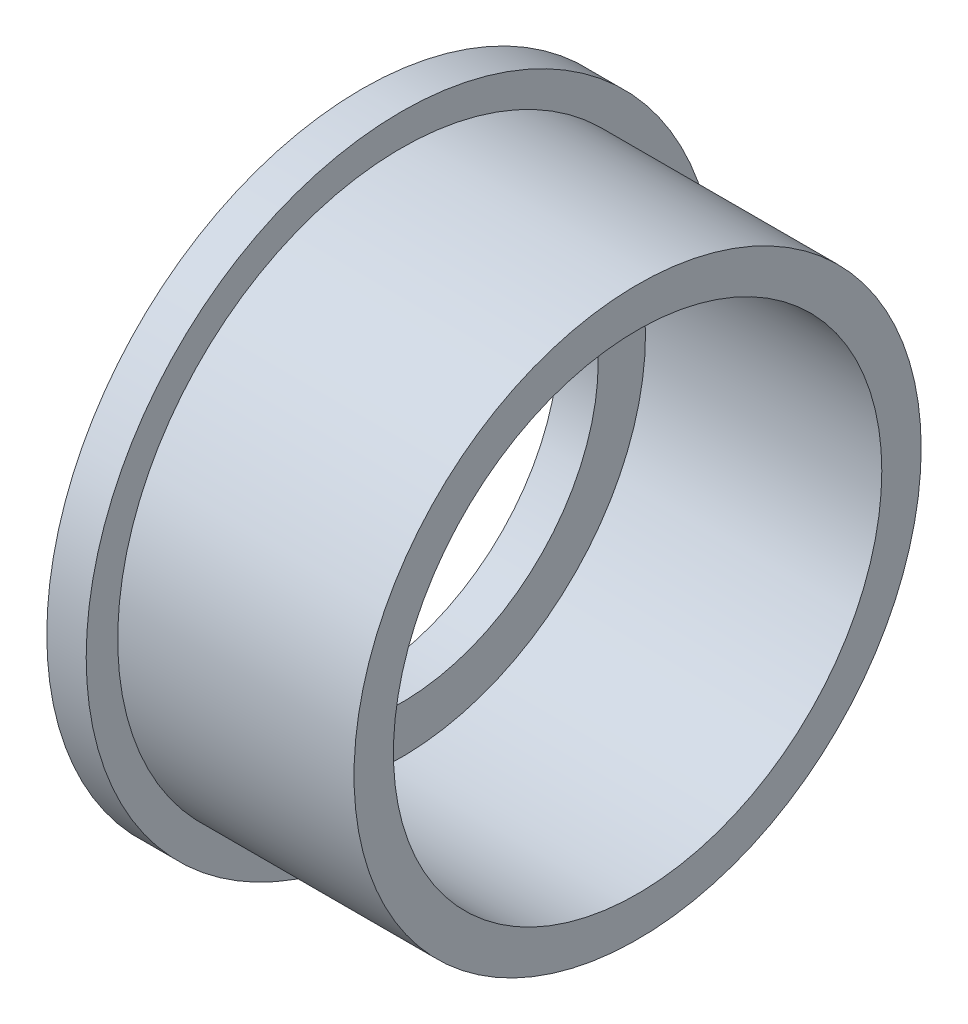
SolidWorks part; units mm, degrees
ref_plane "Front Plane" through (0, 0, 0) normal (1, 0, 0) x (0, 1, 0)
ref_plane "Top Plane" through (0, 0, 0) normal (0, 0, 1) x (0, 1, 0)
ref_plane "Right Plane" through (0, 0, 0) normal (0, 1, 0) x (-1, 0, 0)
sketch "Sketch1" plane through (0, 0, 0) normal (1, 0, 0) x (0, 1, 0)
  circle A0 centre (0, 0) radius 8
  circle A1 centre (0, 0) radius 5
  dimension "D1" = 16
  dimension "D2" = 10
extrude "Boss-Extrude1" add sketch "Sketch1" along normal blind 1
sketch "Sketch2" plane through (1, 0, 0) normal (1, 0, 0) x (0, 1, 0)
  circle A0 centre (0, 0) radius 7.2
  circle A1 centre (0, 0) radius 6.2
  dimension "D1" = 12.4
  dimension "D2" = 1
extrude "Boss-Extrude2" add sketch "Sketch2" along normal blind 6
